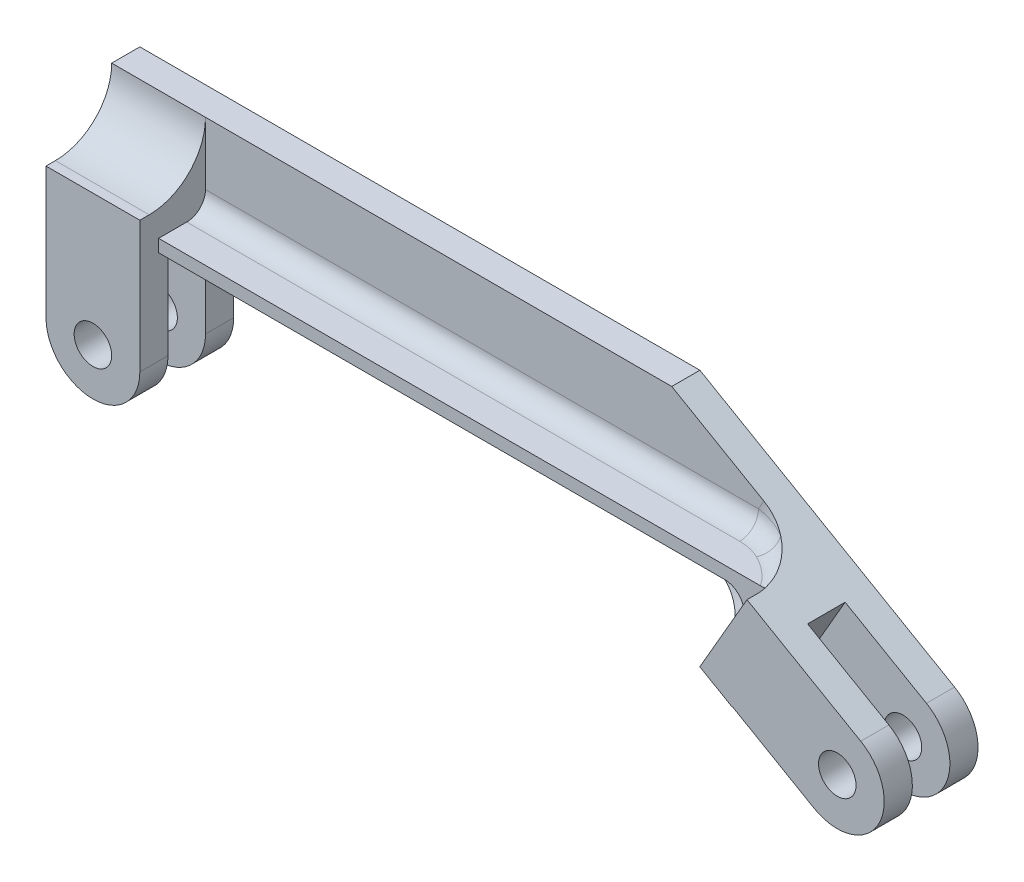
SolidWorks part; units mm, degrees
ref_plane "Front Plane" through (0, 0, 0) normal (0, 0, 1) x (1, 0, 0)
ref_plane "Top Plane" through (0, 0, 0) normal (0, 1, 0) x (1, 0, 0)
ref_plane "Right Plane" through (0, 0, 0) normal (1, 0, 0) x (0, 0, -1)
sketch "Sketch1" plane through (0, 0, 0) normal (0, 0, 1) x (1, 0, 0)
  line L0 (0, 0) -> (0, 15) construction
  line L1 (5, 0) -> (5, 10)
  line L2 (0, 15) -> (53.3452, 15) construction
  line L3 (53.3452, 15) -> (79.326, 0) construction
  line L4 (5, 10) -> (52.0055, 10)
  line L5 (52.0055, 10) -> (76.826, -4.3301)
  line L6 (-5, 0) -> (-5, 20)
  line L7 (-5, 20) -> (54.685, 20)
  line L8 (54.685, 20) -> (81.826, 4.3301)
  circle A0 centre (0, 0) radius 2
  circle A1 centre (0, 0) radius 5
  circle A2 centre (79.326, 0) radius 2
  circle A3 centre (79.326, 0) radius 5
  point P8 (0, 0)
  point P15 (54.215, 9.651)
  dimension "D1" = 4
  dimension "D2" = 3
  dimension "D8" = 4
  dimension "D3" = 150
  dimension "D4" = 30
  dimension "D5" = 5
  dimension "D6" = 5
extrude "Boss-Extrude1" add sketch "Sketch1" along normal blind 3 contours A3 A1 L4 | A1 A0 | A3 A2 region at (34.2275, 12.6199, 0) region at (0, -4.8586, 0) region at (75.1183, 2.4293, 0)
sketch "Sketch4" plane through (0, 0, 3) normal (0, 0, 1) x (1, 0, 0)
  line L0 (-5, 10) -> (5, 10)
  line L1 (-5, 10) -> (-5, 14)
  line L2 (5, 10) -> (5, 14)
  line L3 (-5, 14) -> (5, 14)
  line L4 (-5, 0) -> (-5, 20) construction
  line L5 (73.1657, 9.3301) -> (69.7016, 11.3301)
  line L6 (73.1657, 9.3301) -> (68.139, 0.6236)
  line L7 (69.7016, 11.3301) -> (64.6749, 2.6236)
  line L8 (68.139, 0.6236) -> (64.6749, 2.6236)
  line L9 (54.685, 20) -> (81.826, 4.3301) construction
  circle A0 centre (79.326, 0) radius 2 construction
  dimension "D1" = 10
  dimension "D2" = 4
  dimension "D3" = 10
  dimension "D4" = 10
  dimension "D5" = 4
extrude "Boss-Extrude4" add sketch "Sketch4" along normal blind 4
sketch "Sketch5" plane through (0, 0, 7) normal (0, 0, 1) x (1, 0, 0)
  line L3 (5, 10) -> (-5, 10)
  line L4 (-5, 10) -> (-5, 0)
  line L5 (5, 0) -> (5, 10)
  line L6 (5, 10) -> (-5, 10)
  line L7 (-5, 10) -> (-5, 0)
  line L8 (5, 0) -> (5, 10)
  line L9 (81.826, 4.3301) -> (73.1657, 9.3301)
  line L10 (73.1657, 9.3301) -> (68.1657, 0.6699)
  line L11 (68.1657, 0.6699) -> (76.826, -4.3301)
  line L12 (81.826, 4.3301) -> (73.1657, 9.3301)
  line L13 (73.1657, 9.3301) -> (68.1657, 0.6699)
  line L14 (68.1657, 0.6699) -> (76.826, -4.3301)
  line L16 (68.139, 0.6236) -> (73.1657, 9.3301)
  line L17 (73.1657, 9.3301) -> (69.7016, 11.3301)
  line L18 (69.7016, 11.3301) -> (64.6749, 2.6236)
  line L19 (64.6749, 2.6236) -> (68.139, 0.6236)
  line L20 (68.139, 0.6236) -> (73.1657, 9.3301)
  line L21 (73.1657, 9.3301) -> (69.7016, 11.3301)
  line L22 (69.7016, 11.3301) -> (64.6749, 2.6236)
  line L23 (64.6749, 2.6236) -> (68.139, 0.6236)
  line L24 (-5, 14) -> (-5, 10)
  line L25 (-5, 10) -> (5, 10)
  line L26 (5, 10) -> (5, 14)
  line L27 (5, 14) -> (-5, 14)
  line L28 (-5, 14) -> (-5, 10)
  line L29 (-5, 10) -> (5, 10)
  line L30 (5, 10) -> (5, 14)
  line L31 (5, 14) -> (-5, 14)
  circle A0 centre (0, 0) radius 2 construction
  arc A1 (-5, 0) -> (5, 0) centre (0, 0) ccw
  arc A2 (-5, 0) -> (5, 0) centre (0, 0) ccw
  circle A3 centre (0, 0) radius 2
  circle A4 centre (79.326, 0) radius 2 construction
  arc A5 (76.826, -4.3301) -> (81.826, 4.3301) centre (79.326, 0) ccw
  arc A6 (76.826, -4.3301) -> (81.826, 4.3301) centre (79.326, 0) ccw
  circle A7 centre (79.326, 0) radius 2
  line M17 (-5, 14) -> (-5, 10)
  line M18 (-5, 10) -> (5, 10)
  line M19 (5, 10) -> (5, 14)
  line M20 (5, 14) -> (-5, 14)
  dimension "D1" = 0
  dimension "D2" = 0
  dimension "D3" = 0
  dimension "D4" = 0
extrude "Boss-Extrude5" add sketch "Sketch5" along normal blind 3 contours L7 A2 L8 A3 M18 | M20 M17 M18 M19 | L14 A6 L12 L13 A7 | L22 L23 L20 L13 L21 region at (0, 3.2885, 7) region at (0, 12, 7) region at (76.478, 1.6443, 7) region at (68.9203, 5.9768, 7)
fillet "Fillet2" radius 6 2 edges at (0, 14, 3) (67.2016, 7, 3)
sketch "Sketch6" plane through (0, 0, 3) normal (0, 0, 1) x (1, 0, 0)
  line L1 (5, 10) -> (69.7016, 10)
  line L2 (5, 10) -> (5, 11.3301)
  line L3 (5, 11.3301) -> (69.7016, 11.3301)
  line L4 (69.7016, 10) -> (69.7016, 11.3301)
extrude "Boss-Extrude6" add sketch "Sketch6" along normal blind 5
fillet "Fillet3" radius 2 4 edges at (67.2456, 11.3301, 4.4174) (66.4776, 10, 4.4174) (33.8867, 11.3301, 3) (57.0055, 10, 3)
